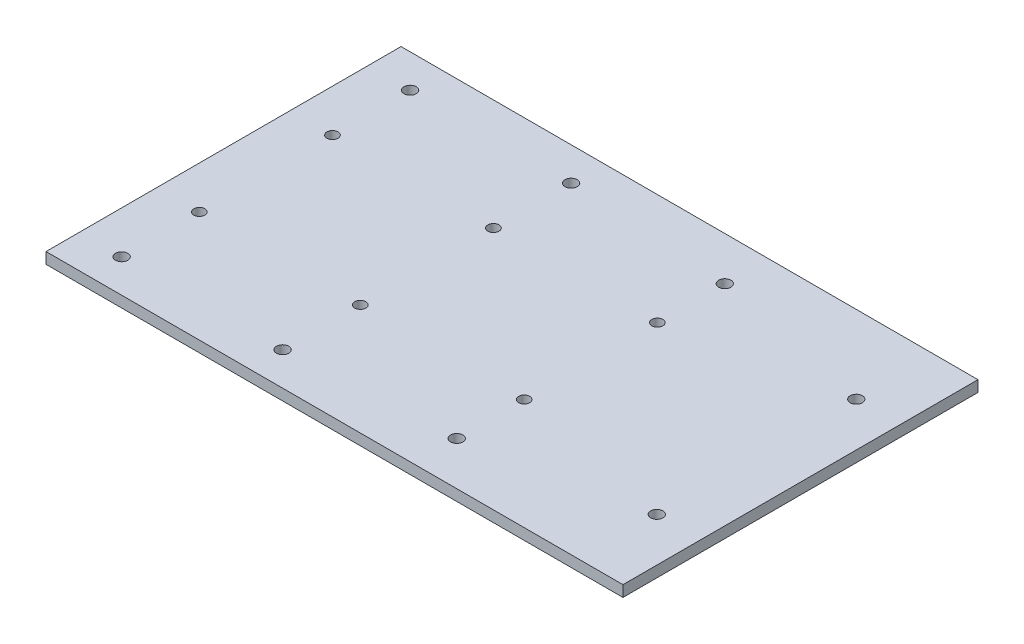
SolidWorks part; units mm, degrees
material "6061-T6 (SS)"
ref_plane "Front Plane" through (0, 0, 0) normal (0, 0, 1) x (1, 0, 0)
ref_plane "Top Plane" through (0, 0, 0) normal (0, 1, 0) x (1, 0, 0)
ref_plane "Right Plane" through (0, 0, 0) normal (1, 0, 0) x (0, 0, -1)
sketch "Sketch1" plane through (0, 0, 0) normal (0, 1, 0) x (1, 0, 0)
  line L1 (-165.1, -101.6) -> (165.1, -101.6)
  line L2 (-165.1, -101.6) -> (-165.1, 101.6)
  line L3 (-165.1, 101.6) -> (165.1, 101.6)
  line L4 (165.1, -101.6) -> (165.1, 101.6)
  line L5 (-165.1, -101.6) -> (165.1, 101.6) construction
  line L6 (-165.1, 101.6) -> (165.1, -101.6) construction
  point P0 (0, 0)
  dimension "D1" = 330.2
  dimension "D2" = 203.2
extrude "Boss-Extrude1" add sketch "Sketch1" along normal blind 6.35
sketch "Sketch2" plane through (0, 6.35, 0) normal (0, 1, 0) x (1, 0, 0)
  line L0 (-140.8516, 82.55) -> (-140.8516, -82.55) construction
  line L1 (-48.7159, 82.55) -> (-48.7159, -82.55) construction
  line L2 (45.0841, 76.701) -> (45.0841, -76.699) construction
  line L3 (-140.8516, 0) -> (45.0841, 0.001) construction
  line L4 (-140.8514, -38.1) -> (45.0843, -38.099) construction
  line L5 (-140.8518, 38.1) -> (45.0839, 38.101) construction
  point P0 (-140.8516, -82.55)
  point P1 (-48.7159, -82.55)
  point P3 (45.0841, -76.699)
  point P5 (45.0841, 76.701)
  point P7 (-48.7159, 82.55)
  point P9 (-140.8516, 82.55)
  point P25 (-48.7159, -38.0995)
  point P26 (-140.8514, -38.1)
  point P27 (-48.7159, 38.1005)
  point P28 (45.0839, 38.101)
  point P29 (45.0843, -38.099)
  point P30 (-140.8518, 38.1)
  point P31 (139.9541, 57.072)
  point P32 (139.9541, -57.072)
  dimension "D1" = 38.1
  dimension "D2" = 38.1
hole_wizard "1/4 (0.25) Press Dowel Hole1" positions "Sketch3" profile "Sketch4" hole size "1/4" standard "ANSI Inch" end condition through all
sketch "Sketch3" plane through (0, 6.35, 0) normal (0, 1, 0) x (1, 0, 0)
  point P0 (-140.8518, 38.1)
  point P3 (-140.8514, -38.1)
  point P6 (-48.7159, -38.0995)
  point P9 (-48.7159, 38.1005)
  point P12 (45.0839, 38.101)
  point P15 (45.0843, -38.099)
sketch "Sketch4" plane through (-140.8518, 6.35, -38.1) normal (1, 0, 0) x (0, 0, 1)
  line L0 (0, 0) -> (0, 6.35)
  line L1 (0, 6.35) -> (3.175, 6.35)
  line L2 (3.175, 6.35) -> (3.175, 0)
  line L5 (3.175, 0) -> (0, 0)
  line L11 (0, -6.35) -> (0, 107.95) construction
  dimension "Thru Hole Dia." = 6.35
  dimension "Thru Hole Depth" = 6.35
hole_wizard "M8x1.0 Tapped Hole1" positions "Sketch5" profile "Sketch6" tap size "M8x1.0" standard "ANSI Metric" end condition through all
sketch "Sketch5" plane through (0, 6.35, 0) normal (0, 1, 0) x (1, 0, 0)
  point P0 (-140.8516, 82.55)
  point P3 (-48.7159, 82.55)
  point P6 (45.0841, 76.701)
  point P9 (45.0841, -76.699)
  point P12 (-48.7159, -82.55)
  point P15 (-140.8516, -82.55)
  point P19 (139.9541, 57.072)
  point P22 (139.9541, -57.072)
sketch "Sketch6" plane through (-140.8516, 6.35, -82.55) normal (1, 0, 0) x (0, 0, 1)
  line L0 (0, 0) -> (0, 6.35)
  line L1 (0, 6.35) -> (3.5, 6.35)
  line L2 (3.5, 6.35) -> (3.5, 0)
  line L5 (3.5, 0) -> (0, 0)
  line L11 (0, -6.35) -> (0, 107.95) construction
  dimension "Thread Major Dia." = 7
  dimension "Thru Tap Drill Depth" = 6.35
sketch "Sketch7"
